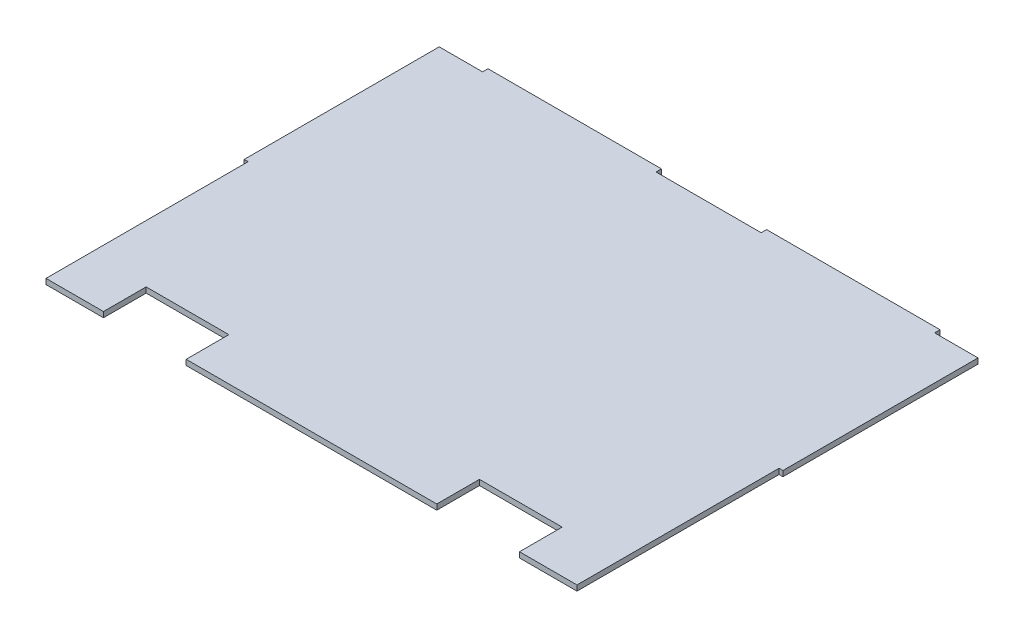
SolidWorks part; units mm, degrees
material "Custom Plastic"
ref_plane "X-Y Datum" through (0, 0, 0) normal (0, 0, 1) x (1, 0, 0)
ref_plane "X-Z Datum" through (0, 0, 0) normal (0, 1, 0) x (1, 0, 0)
ref_plane "Y-Z Datum" through (0, 0, 0) normal (1, 0, 0) x (0, 0, -1)
sketch "Sketch1" plane through (0, 0, 0) normal (0, 0, 1) x (1, 0, 0)
  line L1 (-157.7875, -1.5875) -> (157.7875, -1.5875)
  line L2 (-157.7875, -1.5875) -> (-157.7875, 1.5875)
  line L3 (-157.7875, 1.5875) -> (157.7875, 1.5875)
  line L4 (157.7875, -1.5875) -> (157.7875, 1.5875)
  line L5 (-157.7875, -1.5875) -> (157.7875, 1.5875) construction
  line L6 (-157.7875, 1.5875) -> (157.7875, -1.5875) construction
  point P0 (0, 0)
  dimension "D1" = 315.575
  dimension "D2" = 3.175
extrude "Boss-Extrude1" add sketch "Sketch1" along normal blind 235.775
sketch "Sketch3" plane through (0, 0, 0) normal (0, 0, -1) x (-1, 0, 0)
  line L0 (-157.7875, 0) -> (-81.5875, 0) construction
  line L1 (-157.7875, -1.5875) -> (-157.7875, 1.5875) construction
  line L2 (-157.7875, 1.5875) -> (157.7875, 1.5875) construction
  line L3 (-132.3875, -1.5875) -> (-30.7875, -1.5875)
  line L4 (-132.3875, -1.5875) -> (-132.3875, 1.5875)
  line L5 (-132.3875, 1.5875) -> (-30.7875, 1.5875)
  line L6 (-30.7875, -1.5875) -> (-30.7875, 1.5875)
  line L7 (-132.3875, -1.5875) -> (-30.7875, 1.5875) construction
  line L8 (-132.3875, 1.5875) -> (-30.7875, -1.5875) construction
  line L14 (-157.7875, 1.5875) -> (-132.3875, 1.5875)
  line L15 (-157.7875, 1.5875) -> (-157.7875, -1.5875)
  line L16 (-157.7875, -1.5875) -> (-132.3875, -1.5875)
  line L17 (-132.3875, 1.5875) -> (-132.3875, -1.5875)
  line L19 (-30.7875, 1.5875) -> (-30.7875, -1.5875)
  line L20 (0, 43.0151) -> (0, -43.0151) construction
  line L21 (30.7875, -1.5875) -> (30.7875, 1.5875)
  line L22 (132.3875, -1.5875) -> (132.3875, 1.5875)
  line L23 (132.3875, 1.5875) -> (30.7875, 1.5875)
  line L24 (132.3875, -1.5875) -> (30.7875, 1.5875) construction
  line L25 (132.3875, -1.5875) -> (30.7875, -1.5875)
  line L26 (132.3875, 1.5875) -> (30.7875, -1.5875) construction
  line M2 (-157.7875, 1.5875) -> (-157.7875, -1.5875)
  line M3 (-157.7875, -1.5875) -> (157.7875, -1.5875)
  line M4 (157.7875, -1.5875) -> (157.7875, 1.5875)
  line M5 (157.7875, 1.5875) -> (-157.7875, 1.5875)
  dimension "D1" = 76.2
  dimension "D2" = 101.6
extrude "Cut-Extrude1" cut sketch "Sketch3" against normal blind 3.175 contours L4 M3 M5 M2 | L6 M3 M5 | M3 M4 M5 region at (145.0875, 0, 0) region at (0, 0, 0) region at (-145.0875, 0, 0)
sketch "Sketch5" plane through (0, 1.5875, 0) normal (0, 1, 0) x (1, 0, 0)
  line L1 (-157.7875, -235.775) -> (-155.5015, -235.775)
  line L3 (-157.7875, -235.775) -> (-157.7875, -117.411)
  line L5 (-157.7875, -117.411) -> (-155.5015, -117.411)
  line L6 (-155.5015, -235.775) -> (-155.5015, -117.411)
  line M11 (-157.7875, -3.175) -> (-157.7875, -235.775)
  line M12 (-157.7875, -235.775) -> (157.7875, -235.775)
  dimension "D1" = 118.364
  dimension "D2" = 2.286
extrude "Cut-Extrude2" cut sketch "Sketch5" against normal blind 3.175 and the other way through all contours M12 M11 region at (-156.6445, 1.5875, 176.593)
mirror "Mirror1" about plane through (0, 0, 0) normal (1, 0, 0) of "Cut-Extrude2"
sketch "Sketch6" plane through (0, 1.5875, 0) normal (0, 1, 0) x (1, 0, 0)
  line L5 (155.5015, -235.775) -> (-155.5015, -235.775) construction
  line L6 (-121.8431, -210.775) -> (-73.389, -210.775)
  line L7 (-121.8431, -210.775) -> (-121.8431, -235.775)
  line L8 (-121.8431, -235.775) -> (-73.389, -235.775)
  line L9 (-73.389, -210.775) -> (-73.389, -235.775)
extrude "Cut-Extrude4" cut sketch "Sketch6" against normal through all
mirror "Mirror2" about plane through (0, 0, 0) normal (1, 0, 0) of "Cut-Extrude4"
